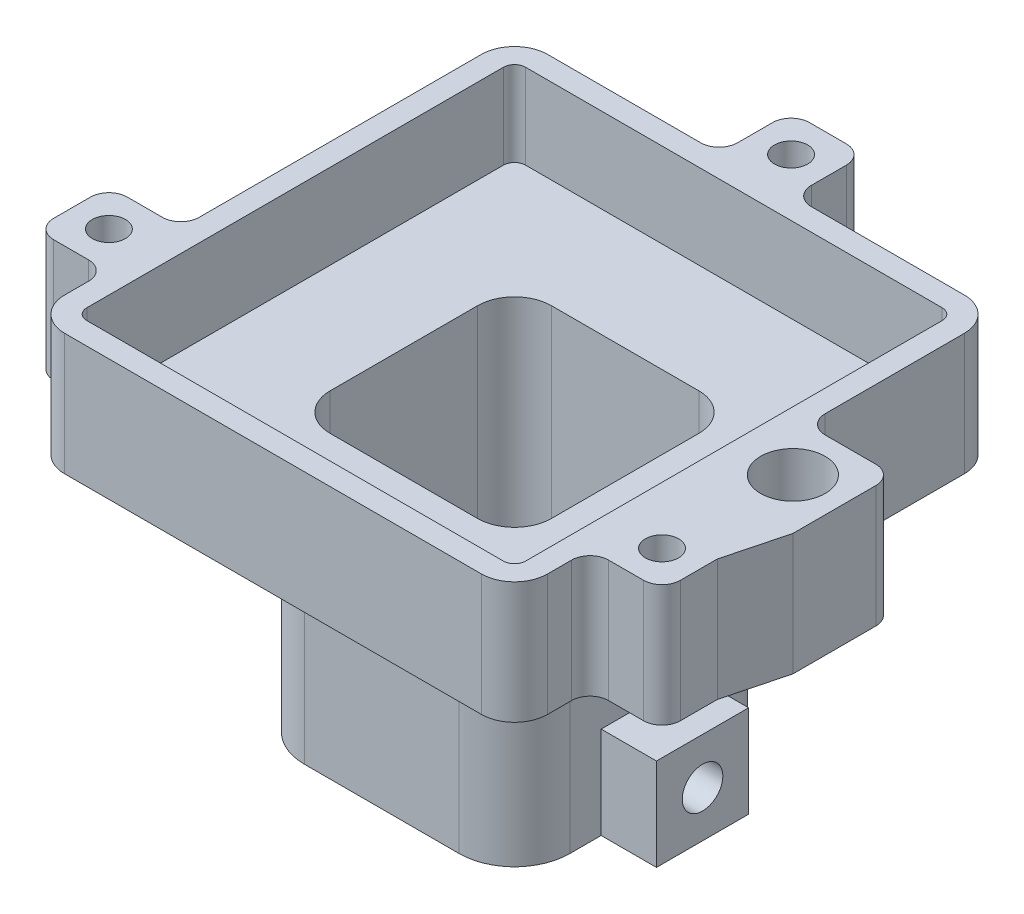
SolidWorks part; units mm, degrees
note: '?' marks a value the reader was unsure of.
material "ABS PC"
ref_plane "Front Plane" through (0, 0, 0) normal (0, 0, 1) x (1, 0, 0)
ref_plane "Top Plane" through (0, 0, 0) normal (0, 1, 0) x (1, 0, 0)
ref_plane "Right Plane" through (0, 0, 0) normal (1, 0, 0) x (0, 0, -1)
ref_axis "Center Axis" through (0, 12.161, 0) along (0, -1, 0)?
sketch "Quarter Reference" plane through (0, 0, 0) normal (0, 0, 1) x (1, 0, 0)
  circle A0 centre (0, 0) radius 12.13
  dimension "D1" = 24.26
sketch "Driving Dimensions"
  point P0 (1.5, 3.48)
  point P1 (2.05, 1.869)
  point P2 (0, -7.25)
  point P3 (2.05, 0.869)
  point P5 (5.7, 9.37)
  point P7 (5.7, 11.67)
  point P9 (0, -7.43)
  point P13 (1.5, 2.369)
  point P15 (1.5, 4.849)
  dimension "D1" = 1.369
  dimension "D2" = 0
  dimension "D7" = 0
  dimension "D9" = 2.3
  dimension "D3" = 1.5
  dimension "D4" = 1
  dimension "D5" = 0.5
  dimension "D6" = 2.05
  dimension "D8" = 2.48
  dimension "D11" = 5.89
  dimension "D12" = 10.91
  dimension "D13" = 5.7
  dimension "D14" = 16.62
  dimension "D15" = 0
other "AlignGroup1" parameters "D1"=3.1925, "D2"=0, "D3"=2, "D4"=2, "D5"=3, "D6"=5.7, "D7"=0, "D8"=2.1939, "D9"=10.92, "D10"=11.67, "D11"=0.5013, "D12"=0.5, "D13"=1.5, "1"=16.304, "D14"=2, "D15"=0.712
other "AlignGroup2"
ref_plane "CMOS Sensor Bottom" through (0, 9.37, 0) normal (0, 1, 0) x (1, 0, 0)
ref_plane "CMOS Sensor Top" through (0, 11.67, 0) normal (0, 1, 0) x (1, 0, 0)
ref_plane "Brain Surface (approx.)" through (0, -10.13, 0) normal (0, 1, 0) x (1, 0, 0)
sketch "Sketch4" plane through (0, 9.37, 0) normal (0, 1, 0) x (1, 0, 0)
  line L0 (-6.55, 5.65) -> (-6.55, -5.65)
  line L1 (-5.65, 5.95) -> (5.65, 5.95)
  line L2 (-5.95, 5.65) -> (-5.95, -5.65)
  line L3 (-5.65, -5.95) -> (5.65, -5.95)
  line L4 (5.95, 5.65) -> (5.95, -5.65)
  line L5 (-5.95, 5.95) -> (5.95, -5.95) construction
  line L6 (-5.95, -5.95) -> (5.95, 5.95) construction
  line L7 (-5.65, -6.55) -> (5.65, -6.55)
  line L8 (6.55, 5.65) -> (6.55, -5.65)
  line L9 (-5.65, 6.55) -> (5.65, 6.55)
  arc A0 (5.65, 5.95) -> (5.95, 5.65) centre (5.65, 5.65) cw
  arc A1 (-5.65, 5.95) -> (-5.95, 5.65) centre (-5.65, 5.65) ccw
  arc A2 (-5.95, -5.65) -> (-5.65, -5.95) centre (-5.65, -5.65) ccw
  arc A3 (5.65, -5.95) -> (5.95, -5.65) centre (5.65, -5.65) ccw
  arc A4 (-6.55, -5.65) -> (-5.65, -6.55) centre (-5.65, -5.65) ccw
  arc A5 (5.65, -6.55) -> (6.55, -5.65) centre (5.65, -5.65) ccw
  arc A6 (5.65, 6.55) -> (6.55, 5.65) centre (5.65, 5.65) cw
  arc A7 (-5.65, 6.55) -> (-6.55, 5.65) centre (-5.65, 5.65) ccw
  point P0 (0, 0)
  dimension "D2" = 0.3
  dimension "D1" = 0.25
  dimension "D3" = 0.6
extrude "Boss-Extrude1" add sketch "Sketch4" along normal up to surface (2.3 mm away) up to plane "CMOS Sensor Top"
sketch "Sketch20" plane through (0, 9.37, 0) normal (0, -1, 0) x (1, 0, 0)
  line L0 (5.65, -6.55) -> (-5.65, -6.55) construction
  line L1 (-6.55, -5.65) -> (-6.55, 5.65) construction
  line L2 (-5.65, 6.55) -> (5.65, 6.55) construction
  line L3 (6.55, 5.65) -> (6.55, -5.65) construction
  line L4 (5.65, -6.55) -> (-5.65, -6.55)
  line L5 (-6.55, -5.65) -> (-6.55, 5.65)
  line L6 (-5.65, 6.55) -> (5.65, 6.55)
  line L7 (6.55, 5.65) -> (6.55, -5.65)
  arc A0 (5.65, -6.55) -> (6.55, -5.65) centre (5.65, -5.65) ccw construction
  arc A1 (-6.55, -5.65) -> (-5.65, -6.55) centre (-5.65, -5.65) ccw construction
  arc A2 (-5.65, 6.55) -> (-6.55, 5.65) centre (-5.65, 5.65) ccw construction
  arc A3 (6.55, 5.65) -> (5.65, 6.55) centre (5.65, 5.65) ccw construction
  arc A4 (5.65, -6.55) -> (6.55, -5.65) centre (5.65, -5.65) ccw
  arc A5 (-6.55, -5.65) -> (-5.65, -6.55) centre (-5.65, -5.65) ccw
  arc A6 (-5.65, 6.55) -> (-6.55, 5.65) centre (-5.65, 5.65) ccw
  arc A7 (6.55, 5.65) -> (5.65, 6.55) centre (5.65, 5.65) ccw
extrude "Boss-Extrude2" add sketch "Sketch20" along normal blind 1
sketch "Sketch19" plane through (0, 11.67, 0) normal (0, 1, 0) x (1, 0, 0)
  line L0 (-1, 6.55) -> (-1, 8.5)
  line L1 (5.65, 6.55) -> (-5.65, 6.55) construction
  line L2 (-1, 8.5) -> (1, 8.5)
  line L3 (1, 8.5) -> (1, 6.55)
  line L4 (1, 6.55) -> (-1, 6.55)
  line L5 (-6.55, 5.65) -> (-6.55, -5.65) construction
  line L6 (-6.55, -2.5) -> (-8.5, -2.5)
  line L7 (-6.55, -2.5) -> (-6.55, -4.5)
  line L8 (-6.55, -4.5) -> (-8.5, -4.5)
  line L9 (-8.5, -2.5) -> (-8.5, -4.5)
  line L10 (6.55, -5.65) -> (6.55, 5.65) construction
  line L11 (6.55, -2.5) -> (8.5, -2.5)
  line L12 (6.55, -2.5) -> (6.55, -4.5)
  line L13 (6.55, -4.5) -> (8.5, -4.5)
  line L14 (8.5, -2.5) -> (8.5, -4.5)
  circle A0 centre (0, 7.5) radius 0.45
  circle A1 centre (-7.5, -3.5) radius 0.45
  circle A2 centre (7.5, -3.5) radius 0.45
  point P25 (-7.525, -2.5)
  dimension "D1" = 7.5
  dimension "D3" = 0.9
  dimension "D2" = 2
  dimension "D4" = 1
  dimension "D5" = 1
  dimension "D6" = 8.5
  dimension "D7" = 7.5
  dimension "D8" = 7.5
  dimension "D9" = 3.5
  dimension "D10" = 3.5
  dimension "D11" = 2
  dimension "D12" = 2
  dimension "D13" = 8.5
  dimension "D14" = 8.5
  dimension "D15" = 1
  dimension "D16" = 1
extrude "CMOS Mounting Holes" add sketch "Sketch19" against normal up to surface (3.3 mm away) up to face at (0, 8.37, 0)
fillet "Fillet1" radius 0.5 12 edges at (6.55, 10.02, 2.5) (8.5, 10.02, 2.5) (8.5, 10.02, 4.5) (6.55, 10.02, 4.5) (-6.55, 10.02, 4.5) (-8.5, 10.02, 4.5) (-8.5, 10.02, 2.5) (-6.55, 10.02, 2.5) (1, 10.02, -6.55) (1, 10.02, -8.5) (-1, 10.02, -8.5) (-1, 10.02, -6.55)
sketch "Sketch21" plane through (0, 8.37, 0) normal (0, -1, 0) x (1, 0, 0)
  line L1 (-3, 3) -> (3, 3)
  line L2 (-3, 3) -> (-3, -3)
  line L3 (-3, -3) -> (3, -3)
  line L4 (3, 3) -> (3, -3)
  line L5 (-3.6, 3.6) -> (3.6, 3.6)
  line L6 (-3.6, 3.6) -> (-3.6, -3.6)
  line L7 (-3.6, -3.6) -> (3.6, -3.6)
  line L8 (3.6, 3.6) -> (3.6, -3.6)
  dimension "D1" = 6
  dimension "D2" = 7.2
  dimension "D3" = 3
  dimension "D4" = 3.6
  dimension "D5" = 3
  dimension "D6" = 3.6
extrude "Column" add sketch "Sketch21" along normal blind 6.52
sketch "Sketch22" plane through (0, 8.37, 0) normal (0, -1, 0) x (1, 0, 0)
  line L0 (-3, -3) -> (3, -3) construction
  line L1 (3, -3) -> (3, 3) construction
  line L2 (3, 3) -> (-3, 3) construction
  line L3 (-3, 3) -> (-3, -3) construction
  line L4 (-3, -3) -> (3, -3)
  line L5 (3, -3) -> (3, 3)
  line L6 (3, 3) -> (-3, 3)
  line L7 (-3, 3) -> (-3, -3)
extrude "Column Extruded Cut" cut sketch "Sketch22" against normal through all
fillet "Column Outside Fillet" radius 1.5 4 edges at (-3.6, 5.11, -3.6) (3.6, 5.11, -3.6) (3.6, 5.11, 3.6) (-3.6, 5.11, 3.6)
fillet "Column Inside Fillet" radius 1 4 edges at (-3, 5.61, 3) (-3, 5.61, -3) (3, 5.61, -3) (3, 5.61, 3)
sketch "Sketch23" plane through (0, 1.85, 0) normal (0, -1, 0) x (1, 0, 0)
  line L2 (2.0201, 4.3012) -> (4.3012, 2.0201) construction
  line L6 (3.6, 2.1) -> (4.6945, 3.1945)
  line L7 (2.1, 3.6) -> (3.1945, 4.6945)
  line L8 (3.1945, 4.6945) -> (4.6945, 3.1945)
  arc A2 (3.6, 2.1) -> (2.1, 3.6) centre (2.1, 2.1) ccw construction
  arc A3 (3.6, 2.1) -> (2.1, 3.6) centre (2.1, 2.1) ccw
  arc A4 (3, 2) -> (2, 3) centre (2, 2) ccw construction
  point P9 (3.1607, 3.1607)
  dimension "D1" = 2.75
extrude "Boss-Extrude5" [suppressed] add sketch "Sketch23" against normal blind 2.5
sketch "Sketch24" [suppressed] plane through (3.9445, 0, 3.9445) normal (0.7071, 0, 0.7071) x (0.7071, 0, -0.7071)
  line L0 (-1.2374, 4.35) -> (1.2374, 1.85) construction
  line L1 (-1.2374, 1.85) -> (1.2374, 4.35) construction
  line L2 (1.2374, 4.35) -> (1.2374, 1.85) construction
  line L3 (1.2374, 4.35) -> (-1.2374, 4.35) construction
  circle A0 centre (0, 3.1) radius 0.45
  dimension "D1" = 0.9
extrude "Cut-Extrude2" [suppressed] cut sketch "Sketch24" against normal up to next
sketch "Sketch25" plane through (3.6, 0, 0) normal (1, 0, 0) x (0, 0, -1)
  line L0 (2.1, 1.85) -> (-2.1, 1.85) construction
  line L1 (1.25, 1.85) -> (-1.25, 1.85)
  line L2 (0, 1.85) -> (0, 4.35) construction
  line L3 (-1.25, 1.85) -> (-1.25, 4.35)
  line L4 (-1.25, 4.35) -> (1.25, 4.35)
  line L5 (1.25, 4.35) -> (1.25, 1.85)
  circle A0 centre (0, 3.1) radius 0.55 construction
  dimension "D2" = 1.1
  dimension "D1" = 2.5
extrude "Set Screw Extrusion" add sketch "Sketch25" along normal blind 1.5
sketch "Sketch26" plane through (5.1, 0, 0) normal (1, 0, 0) x (0, 0, -1)
  circle A0 centre (0, 3.1) radius 0.55 construction
  circle A1 centre (0, 3.1) radius 0.55
extrude "Set Screw Hole" cut sketch "Sketch26" against normal up to next contours A1
sketch "Sketch27" plane through (0, 0, -3.6) normal (0, 0, -1) x (-1, 0, 0)
  line L0 (2.1, 1.85) -> (-2.1, 1.85) construction
  line L1 (-1.4419, 7.3748) -> (1.6081, 7.3748)
  line L2 (-1.4419, 7.3748) -> (-1.4419, 2.2431)
  line L3 (-1.4419, 2.2431) -> (1.6081, 2.2431)
  line L4 (1.6081, 7.3748) -> (1.6081, 2.2431)
  dimension "D1" = 5.1317
  dimension "D2" = 3.05
  dimension "D3" = 0.3931
extrude "Weight Reduction" [suppressed] cut sketch "Sketch27" against normal blind 0.5
pattern_circular "Weight Reduction Revolve" [suppressed] count 3 over 180 about axis through (0, 12.161, 0) along (0, -1, 0)
sketch "Sketch28" plane through (0, 11.67, 0) normal (0, 1, 0) x (1, 0, 0)
  line L0 (6.55, -2) -> (6.55, 5.65) construction
  line L1 (6.55, -2) -> (6.55, 2.8125)
  line L2 (0, 0) -> (12.5279, 0) construction
  line L3 (6.55, 2.8125) -> (7.8, 2.8125)
  line L4 (7.8, -2.5) -> (7.8, 2.8125)
  line L5 (8, -2.5) -> (7.05, -2.5) construction
  line L6 (7.8, -2.5) -> (7.05, -2.5)
  circle A0 centre (7.05, -1.875) radius 0.375
  circle A1 centre (7.05, -0.625) radius 0.375
  circle A2 centre (7.05, 0.625) radius 0.375
  circle A3 centre (7.05, 1.875) radius 0.375
  arc A4 (6.55, -2) -> (7.05, -2.5) centre (7.05, -2) ccw construction
  arc A5 (6.55, -2) -> (7.05, -2.5) centre (7.05, -2) ccw
  dimension "D1" = 0.75
  dimension "D2" = 0.5
  dimension "D3" = 1.25
  dimension "D4" = 1.25
  dimension "D5" = 1.25
  dimension "D6" = 0.625
  dimension "D7" = 1.25
  dimension "D8" = 0.9375
extrude "Small Wire Holes" [suppressed] add sketch "Sketch28" against normal up to surface (3.3 mm away)
fillet "Fillet2" [suppressed] radius 0.5
sketch "Sketch29" plane through (0, 11.67, 0) normal (0, 1, 0) x (1, 0, 0)
  line L0 (6.55, -2) -> (6.55, 5.65) construction
  line L1 (6.55, -2) -> (6.55, 1.375)
  line L2 (0, 0) -> (9.846, 0) construction
  line L3 (6.55, 1.375) -> (8.925, 1.375)
  line L4 (8.925, 1.375) -> (8.925, -1.375)
  line L7 (8, -2.5) -> (7.05, -2.5) construction
  line L8 (8, -2.5) -> (7.05, -2.5)
  line L9 (8.5, -3) -> (8.925, -1.375)
  circle A0 centre (7.55, 0) radius 0.875
  arc A5 (8.5, -3) -> (8, -2.5) centre (8, -3) ccw construction
  arc A6 (6.55, -2) -> (7.05, -2.5) centre (7.05, -2) ccw construction
  arc A7 (8.5, -3) -> (8, -2.5) centre (8, -3) ccw
  arc A8 (6.55, -2) -> (7.05, -2.5) centre (7.05, -2) ccw
  dimension "D2" = 1.75
  dimension "D1" = 1
  dimension "D3" = 1.375
  dimension "D4" = 1.375
extrude "Large Wire Hole" add sketch "Sketch29" against normal up to surface (3.3 mm away) up to face at (7.5, 8.37, 3.05)
fillet "Fillet3" radius 0.5 2 edges at (6.55, 10.02, -1.375) (8.925, 10.02, -1.375)
equation "\"D4@Sketch28\"=\"D3@Sketch28\""
equation "\"D5@Sketch28\"=\"D3@Sketch28\""
equation "\"D6@Sketch28\"=\"D3@Sketch28\"/2"
equation "\"D8@Sketch28\"=\"D3@Sketch28\"*.75"
equation "\"D4@Sketch29\"=\"D3@Sketch29\""
equation "\"D4@Sketch21\"=\"D2@Sketch21\"/2"
equation "\"D6@Sketch21\"=\"D2@Sketch21\"/2"
